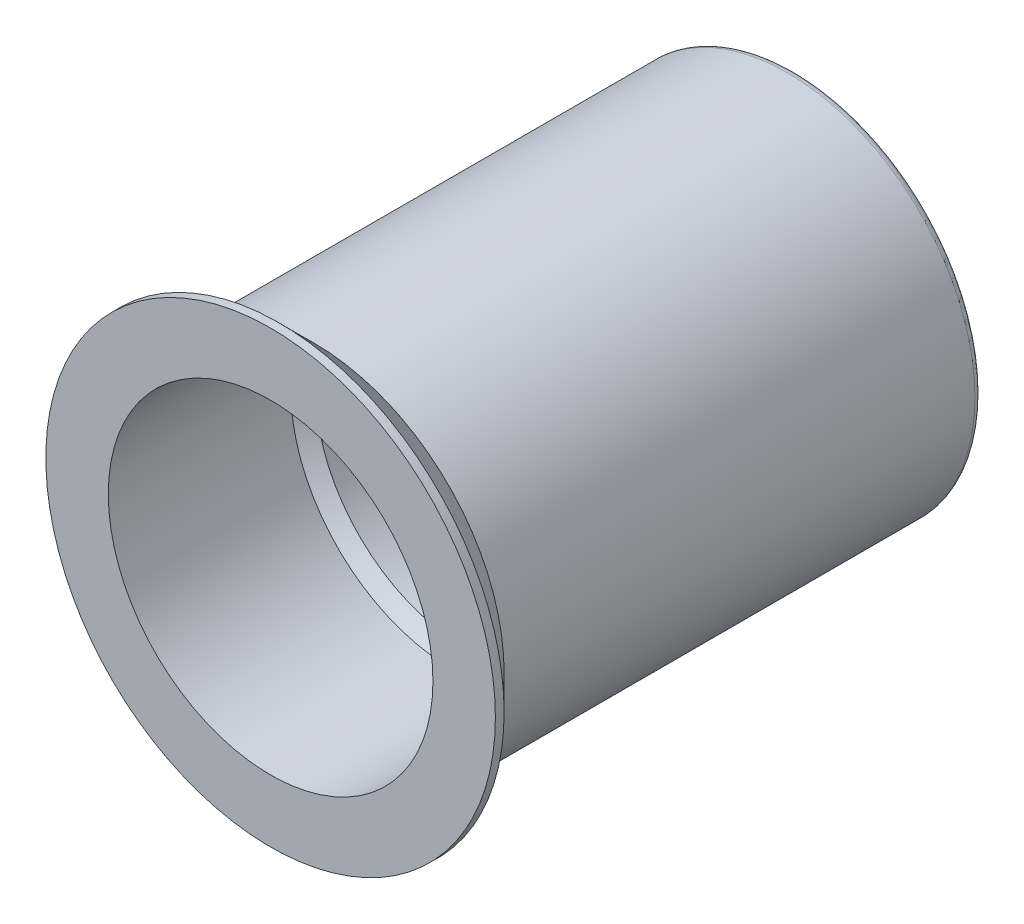
SolidWorks part; units mm, degrees
ref_plane "Front" through (0, 0, 0) normal (0, 0, 1) x (1, 0, 0)
ref_plane "Top" through (0, 0, 0) normal (0, 1, 0) x (1, 0, 0)
ref_plane "Right" through (0, 0, 0) normal (1, 0, 0) x (0, 0, -1)
sketch "Sketch3" plane through (0, 0, 0) normal (0, 0, 1) x (1, 0, 0)
  circle A0 centre (0, 0) radius 9
  dimension "dk" = 18
extrude "BaseHead" add sketch "Sketch3" against normal blind 1.8
sketch "Sketch4" plane through (-3.067, 2.6488, 0) normal (0, 0, -1) x (-1, 0, 0)
  circle A0 centre (-3.067, -2.6488) radius 7.5
  circle A1 centre (-3.067, -2.6488) radius 9 construction
extrude "BaseBody" add sketch "Sketch4" along normal blind 21
sketch "Sketch8" plane through (9, 0, 1.1855) normal (0, 1, 0) x (-1, 0, 0)
  line L0 (9, 2.3542) -> (9, -3.5397) construction
  line L2 (18, -1.5355) -> (16.55, -2.9855)
  line L5 (16.55, -2.9855) -> (18, -2.9855)
  line L7 (18, -2.9855) -> (18, -1.5355)
  dimension "D1" = 45
  dimension "D2" = 15.1
revolve "BearingFace" cut sketch "Sketch8" angle 360 about L0
sketch "Sketch5" plane through (1.6426, -1.4193, 0) normal (0, 0, 1) x (1, 0, 0)
  circle A0 centre (-1.6426, 1.4193) radius 6.5
  circle A1 centre (-1.6426, 1.4193) radius 9 construction
extrude "Hole1" cut sketch "Sketch5" against normal blind 7.3
sketch "Sketch6" plane through (-0.0097, -0.1511, -7.3) normal (0, 0, 1) x (1, 0, 0)
  circle A0 centre (0.0097, 0.1511) radius 6
  circle A1 centre (0.0097, 0.1511) radius 6.5 construction
  dimension "D1" = 12
extrude "Hole2" cut sketch "Sketch6" against normal through all
cosmetic thread "ThreadCosmetic1" [suppressed] parameters "D2"=13
fillet "Fillet1" radius 0.3 2 edges at (-7.5, 0, -21) (7.55, 0, -1.8)
chamfer "Chamfer1" distance 0.5 angle 45 1 edges at (6, 0, -7.3)
chamfer "Chamfer2" distance 0.48 angle 45 1 edges at (6, 0, -21)
sketch "Sketch9" plane through (0, 0, 0) normal (0, 1, 0) x (1, 0, 0)
  line L0 (0, 25.6256) -> (0, 13.1025) construction
  line L1 (5.5, 20.77) -> (6, 20.77)
  line L2 (6, 20.77) -> (6.433, 20.52)
  line L3 (6.433, 20.52) -> (6, 20.27)
  line L4 (6, 20.27) -> (5.5, 20.27)
  line L5 (5.5, 20.27) -> (5.5, 20.77)
  line L6 (-6, 20.52) -> (6, 20.52) construction
  dimension "D2" = 12
revolve "Cut-Revolve10" [suppressed] cut sketch "Sketch9" angle 360 about L0
pattern_linear "LPattern10" [suppressed] count 22 spacing 0.6 along (0, 0, 1) of bodies 107
equation "\"D2@Sketch8\"=\"d@Sketch4\"+ 0.1"
equation "\"D1@Chamfer1\" =  ( \"d1@Sketch5\" - \"D1@Sketch6\" )  / 2"
equation "\"D1@Chamfer2\" = \"D1@Sketch6\" / 25"
equation "\"D1@Sketch9\" = (  \"D2@ThreadCosmetic1\" - \"D1@Sketch6\" )  / 2"
equation "\"D3@LPattern10\" = \"D1@Sketch9\" * 1.2"
equation "\"D1@LPattern10\" = (  \"l@BaseBody\" - \"l1@Hole1\" )  / \"D3@LPattern10\" - 1"
equation "\"D2@Sketch9\" = \"D1@Sketch6\""
